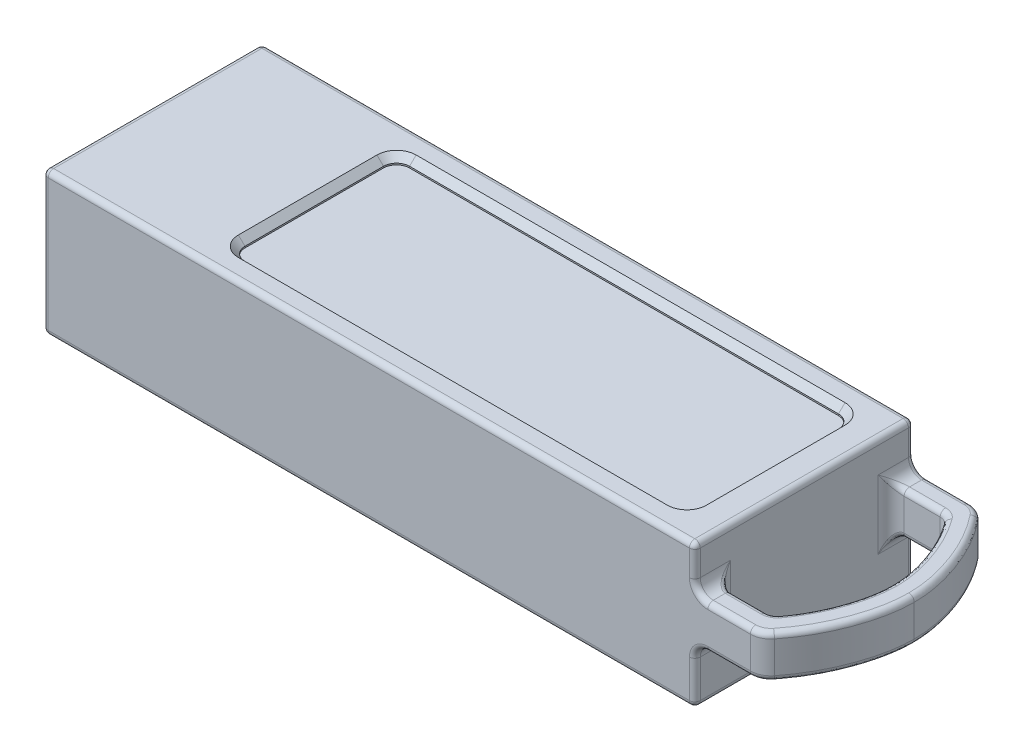
SolidWorks part; units mm, degrees
ref_plane "Front" through (0, 0, 0) normal (0, 0, 1) x (1, 0, 0)
ref_plane "Top" through (0, 0, 0) normal (0, 1, 0) x (1, 0, 0)
ref_plane "Right" through (0, 0, 0) normal (1, 0, 0) x (0, 0, -1)
sketch "Sketch1" plane through (0, 0, 0) normal (0, 1, 0) x (1, 0, 0)
  line L1 (-76.2, -25.6032) -> (76.2, -25.6032)
  line L2 (-76.2, -25.6032) -> (-76.2, 25.6032)
  line L3 (-76.2, 25.6032) -> (76.2, 25.6032)
  line L4 (76.2, -25.6032) -> (76.2, 25.6032)
  line L5 (-76.2, -25.6032) -> (76.2, 25.6032) construction
  line L6 (-76.2, 25.6032) -> (76.2, -25.6032) construction
  point P0 (0, 0)
  dimension "D1" = 51.2064
  dimension "D2" = 152.4
extrude "Boss-Extrude1" add sketch "Sketch1" along normal mid plane 33.401
sketch "Sketch3" plane through (0, 16.7005, 0) normal (0, 1, 0) x (1, 0, 0)
  line L0 (76.2, -25.6032) -> (76.2, 25.6032) construction
  line L1 (67.9831, 19.2405) -> (-38.3667, 19.2405)
  line L2 (67.9831, 19.2405) -> (67.9831, -19.2405)
  line L3 (67.9831, -19.2405) -> (-38.3667, -19.2405)
  line L4 (-38.3667, 19.2405) -> (-38.3667, -19.2405)
  point P6 (67.9831, 0)
  dimension "D1" = 8.2169
  dimension "D2" = 38.481
  dimension "D3" = 106.3498
extrude "Cut-Extrude1" cut sketch "Sketch3" against normal blind 1.8796
fillet "Fillet1" radius 3.048 4 edges at (67.9831, 15.7607, 19.2405) (67.9831, 15.7607, -19.2405) (-38.3667, 15.7607, 19.2405) (-38.3667, 15.7607, -19.2405)
chamfer "Chamfer2" distance 1.524 angle 45 8 edges at (67.9831, 16.7005, 0) (67.0904, 16.7005, -18.3478) (67.0904, 16.7005, 18.3478) (14.8082, 16.7005, -19.2405) (14.8082, 16.7005, 19.2405) (-37.474, 16.7005, -18.3478) (-37.474, 16.7005, 18.3478) (-38.3667, 16.7005, 0)
mirror "Mirror1" about plane through (0, 0, 0) normal (0, 1, 0) of "Cut-Extrude1", "Fillet1"
chamfer "Chamfer3" distance 1.524 angle 45 8 edges at (14.8082, -16.7005, -19.2405) (-37.474, -16.7005, -18.3478) (67.0904, -16.7005, -18.3478) (-38.3667, -16.7005, 0) (67.9831, -16.7005, 0) (-37.474, -16.7005, 18.3478) (67.0904, -16.7005, 18.3478) (14.8082, -16.7005, 19.2405)
sketch "Sketch4" plane through (-76.2, 0, 0) normal (-1, 0, 0) x (0, 0, 1)
  line L0 (-25.6032, -16.7005) -> (25.6032, -16.7005) construction
  line L1 (16.383, 4.1275) -> (-16.383, 4.1275)
  line L2 (19.685, 0.8255) -> (19.685, -8.3185)
  line L3 (16.383, -11.6205) -> (-16.383, -11.6205)
  line L4 (-19.685, 0.8255) -> (-19.685, -8.3185)
  arc A0 (19.685, -8.3185) -> (16.383, -11.6205) centre (16.383, -8.3185) cw
  arc A1 (-16.383, -11.6205) -> (-19.685, -8.3185) centre (-16.383, -8.3185) cw
  arc A2 (16.383, 4.1275) -> (19.685, 0.8255) centre (16.383, 0.8255) cw
  arc A3 (-16.383, 4.1275) -> (-19.685, 0.8255) centre (-16.383, 0.8255) ccw
  point P6 (0, 4.1275)
  point P10 (19.685, -11.6205)
  point P15 (19.685, 4.1275)
  point P18 (-19.685, 4.1275)
  point P19 (16.383, 4.1275)
  dimension "D4" = 3.302
  dimension "D1" = 15.748
  dimension "D2" = 5.08
  dimension "D3" = 39.37
split line "Split Line1"
sketch "Sketch5" plane through (-76.2, 0, 0) normal (-1, 0, 0) x (0, 0, 1)
  line L1 (-17.653, 1.4732) -> (0.3556, 1.4732)
  line L2 (-17.653, 1.4732) -> (-17.653, -8.9662)
  line L3 (-17.653, -8.9662) -> (0.3556, -8.9662)
  line L4 (0.3556, 1.4732) -> (0.3556, -8.9662)
  line L5 (-19.685, 0.8255) -> (-19.685, -8.3185) construction
  line L6 (19.685, -8.3185) -> (19.685, 0.8255) construction
  line L7 (3.429, 0.0635) -> (17.653, 0.0635)
  line L8 (3.429, 0.0635) -> (3.429, -7.5565)
  line L9 (3.429, -7.5565) -> (17.653, -7.5565)
  line L10 (17.653, 0.0635) -> (17.653, -7.5565)
  point P4 (-17.653, -3.7465)
  point P7 (-19.685, -3.7465)
  point P14 (3.429, -3.7465)
  point P15 (0.3556, -3.7465)
  dimension "D1" = 18.0086
  dimension "D2" = 10.4394
  dimension "D3" = 2.032
  dimension "D4" = 14.224
  dimension "D5" = 7.62
  dimension "D6" = 2.032
extrude "Cut-Extrude2" cut sketch "Sketch5" against normal blind 7.9375
fillet "Fillet3" radius 0.508 8 edges at (-72.2312, -7.5565, 17.653) (-72.2312, -7.5565, 3.429) (-72.2312, 0.0635, 17.653) (-72.2312, 0.0635, 3.429) (-72.2312, -8.9662, 0.3556) (-72.2312, -8.9662, -17.653) (-72.2312, 1.4732, 0.3556) (-72.2312, 1.4732, -17.653)
chamfer "Chamfer4" distance 0.762 angle 45 16 edges at (-76.2, -7.5565, 10.541) (-76.2, -7.4077, 17.5042) (-76.2, -7.4077, 3.5778) (-76.2, -3.7465, 17.653) (-76.2, -3.7465, 3.429) (-76.2, -0.0853, 17.5042) (-76.2, -0.0853, 3.5778) (-76.2, 0.0635, 10.541) (-76.2, -8.9662, -8.6487) (-76.2, -8.8174, 0.2068) (-76.2, -8.8174, -17.5042) (-76.2, -3.7465, 0.3556) (-76.2, -3.7465, -17.653) (-76.2, 1.3244, 0.2068) (-76.2, 1.3244, -17.5042) (-76.2, 1.4732, -8.6487)
sketch "Sketch6" plane through (-68.2625, 0, 0) normal (-1, 0, 0) x (0, 0, 1)
  line L0 (-17.653, 0.9652) -> (-17.653, -8.4582) construction
  line L1 (-16.383, -0.8128) -> (-12.9032, -0.8128)
  line L2 (-16.383, -0.8128) -> (-16.383, -6.6802)
  line L3 (-16.383, -6.6802) -> (-12.9032, -6.6802)
  line L4 (-17.653, 0.9652) -> (-17.653, -8.4582) construction
  arc A0 (-12.9032, -0.8128) -> (-12.9032, -6.6802) centre (-12.9032, -3.7465) cw
  circle A1 centre (-12.9032, -3.7465) radius 2.667
  circle A2 centre (-4.7498, -3.7465) radius 2.9464
  circle A3 centre (-4.7498, -3.7465) radius 2.667
  point P8 (-17.653, -3.7465)
  point P9 (-16.383, -3.7465)
  point P15 (-4.7498, -3.7465)
  point P16 (0, 0)
  dimension "D1" = 3.4798
  dimension "D4" = 5.334
  dimension "D5" = 2.2733
  dimension "D6" = 5.8928
  dimension "D7" = 5.334
  dimension "D2" = 5.8674
  dimension "D3" = 1.27
extrude "XT60 Connector Casing" add sketch "Sketch6" along normal offset from surface (7.4295 mm away) 0.508 contours A0 L1 L2 L3 A1 | A2 A3 region at (-68.2625, -0.8997, -14.6431) region at (-68.2625, -3.7465, -7.6129) up to face at (-76.2, 0, 0)
sketch "Sketch7" plane through (-68.2625, 0, 0) normal (-1, 0, 0) x (0, 0, 1)
  circle A24 centre (-12.9032, -3.7465) radius 2.413
  circle A25 centre (-12.9032, -3.7465) radius 2.413
  circle A26 centre (-12.9032, -3.7465) radius 2.159
  circle A27 centre (-4.7498, -3.7465) radius 2.413
  circle A28 centre (-4.7498, -3.7465) radius 2.413
  circle A29 centre (-4.7498, -3.7465) radius 2.159
  dimension "D1" = 0.254
  dimension "D2" = 0.254
  dimension "D3" = 0.254
  dimension "D4" = 0.254
extrude "XT60 Pins" add sketch "Sketch7" along normal offset from surface (6.9215 mm away) 0.508 up to face at (-75.692, -3.7465, -15.5702)
sketch "Sketch9" plane through (-68.2625, 0, 0) normal (-1, 0, 0) x (0, 0, 1)
  line L1 (6.9606, -0.9462) -> (7.547, -0.9462)
  line L2 (6.9606, -0.9462) -> (6.9606, -2.0955)
  line L3 (5.1308, -6.5469) -> (6.123, -6.5469)
  line L4 (7.547, -0.9462) -> (7.547, -2.0955)
  line L5 (13.535, -0.9462) -> (13.535, -2.0955)
  line L6 (8.6788, -2.8124) -> (9.6948, -2.8124)
  line L7 (5.1308, -2.0955) -> (15.9512, -2.0955)
  line L8 (5.1308, -2.0955) -> (5.1308, -5.3975)
  line L9 (5.1308, -5.3975) -> (15.9512, -5.3975)
  line L10 (15.9512, -2.0955) -> (15.9512, -5.3975)
  line L11 (6.123, -2.8124) -> (7.139, -2.8124)
  line L12 (6.123, -2.8124) -> (6.123, -3.8284)
  line L13 (6.123, -3.8284) -> (7.139, -3.8284)
  line L14 (7.139, -2.8124) -> (7.139, -3.8284)
  line L15 (8.6788, -2.8124) -> (8.6788, -3.8284)
  line L16 (8.6788, -3.8284) -> (9.6948, -3.8284)
  line L17 (9.6948, -2.8124) -> (9.6948, -3.8284)
  line L18 (11.2345, -2.8124) -> (12.2505, -2.8124)
  line L19 (11.2345, -2.8124) -> (11.2345, -3.8284)
  line L20 (11.2345, -3.8284) -> (12.2505, -3.8284)
  line L21 (12.2505, -2.8124) -> (12.2505, -3.8284)
  line L22 (13.7902, -2.8124) -> (14.8062, -2.8124)
  line L23 (13.7902, -2.8124) -> (13.7902, -3.8284)
  line L24 (13.7902, -3.8284) -> (14.8062, -3.8284)
  line L25 (14.8062, -2.8124) -> (14.8062, -3.8284)
  line L26 (14.1214, -0.9462) -> (14.1214, -2.0955)
  line L27 (5.1308, -6.5469) -> (5.1308, -5.3975)
  line L28 (6.123, -6.5469) -> (6.123, -5.3975)
  line L29 (7.139, -6.5469) -> (7.139, -5.3975)
  line L30 (8.6788, -6.5469) -> (8.6788, -5.3975)
  line L31 (9.6948, -6.5469) -> (9.6948, -5.3975)
  line L32 (11.2345, -6.5469) -> (11.2345, -5.3975)
  line L33 (12.2505, -6.5469) -> (12.2505, -5.3975)
  line L34 (13.7902, -6.5469) -> (13.7902, -5.3975)
  line L35 (14.8062, -6.5469) -> (14.8062, -5.3975)
  line L36 (10.541, -0.9462) -> (10.541, -6.5469) construction
  line L37 (15.9512, -6.5469) -> (15.9512, -5.3975)
  line L39 (13.535, -0.9462) -> (14.1214, -0.9462)
  line L40 (7.139, -6.5469) -> (8.6788, -6.5469)
  line L41 (9.6948, -6.5469) -> (11.2345, -6.5469)
  line L42 (12.2505, -6.5469) -> (13.7902, -6.5469)
  line L43 (14.8062, -6.5469) -> (15.9512, -6.5469)
  dimension "D3" = 3.302
  dimension "D4" = 1.016
  dimension "D5" = 1.016
  dimension "D6" = 4
extrude "Boss-Extrude4" add sketch "Sketch9" along normal offset from surface (6.4135 mm away) 1.524 contours L3 L28 L9 L27 | L36 L7 L8 L9 L11 L14 L13 L12 L6 L17 L16 L15 | L29 L40 L30 L9 | L9 L36 L41 L32 | L36 L9 L31 L41 | L7 L36 L9 L10 L22 L25 L24 L23 L18 L21 L20 L19 | L33 L42 L34 L9 | L35 L43 L37 L9 region at (-68.2625, -3.8022, 7.8264) region at (-68.2625, -3.8022, 13.2756) region at (-68.2625, -5.9722, 5.6269) region at (-68.2625, -5.9722, 10.1179) region at (-68.2625, -5.9722, 10.8877) region at (-68.2625, -5.9722, 7.9089) region at (-68.2625, -5.9722, 13.0203) region at (-68.2625, -5.9722, 15.3787) up to face at (-76.2, 0, 0)
extrude "Boss-Extrude6" add sketch "Sketch9<5>" along normal offset from surface (5.9055 mm away) 0.508 contours L2 L7 L4 L1 | L39 L5 L7 L26 region at (-68.2625, -1.5208, 7.2538) region at (-68.2625, -1.5208, 13.8282) up to face at (-74.676, -3.3204, 11.7425)
sketch "Sketch9<5>" plane through (-68.2625, 0, 0) normal (-1, 0, 0) x (0, 0, 1) same geometry as "Sketch9"
sketch "Sketch2" plane through (76.2, 0, 0) normal (1, 0, 0) x (0, 0, -1)
  line L0 (25.6032, 16.7005) -> (25.6032, -16.7005) construction
  line L1 (25.6032, 6.4008) -> (-25.6032, 6.4008)
  line L2 (25.6032, 6.4008) -> (25.6032, -3.5687)
  line L3 (25.6032, -3.5687) -> (-25.6032, -3.5687)
  line L4 (-25.6032, 6.4008) -> (-25.6032, -3.5687)
  line L5 (-25.6032, 16.7005) -> (25.6032, 16.7005) construction
  line L6 (-25.6032, 16.7005) -> (-25.6032, -16.7005) construction
  point P6 (19.4182, 25.0944)
  dimension "D1" = 9.9695
  dimension "D3" = 10.2997
extrude "Boss-Extrude7" add sketch "Sketch2" along normal blind 25.6794
sketch "Sketch10" plane through (0, 6.4008, 0) normal (0, 1, 0) x (1, 0, 0)
  line L0 (76.2, 0) -> (101.8794, 0) construction
  line L3 (76.2, 25.6032) -> (76.2, -25.6032) construction
  line L4 (101.8794, 25.6032) -> (101.8794, -25.6032) construction
  line L5 (76.2, 25.6032) -> (89.1783, 25.6032)
  line L7 (76.2, -25.6032) -> (89.1783, -25.6032)
  line L8 (76.2, 20.2692) -> (88.9311, 20.2692)
  line L9 (76.2, -20.2692) -> (88.9311, -20.2692)
  arc A0 (89.1783, 25.6032) -> (92.9662, 23.7676) centre (89.1783, 20.7772) cw
  arc A1 (89.1783, -25.6032) -> (92.9662, -23.7676) centre (89.1783, -20.7772) ccw
  arc A2 (88.9311, 20.2692) -> (88.9311, 20.2692) centre (88.9311, 20.2692) cw
  arc A3 (88.9311, -20.2692) -> (88.9311, -20.2692) centre (88.9311, -20.2692) ccw
  spline S0 degree 3 poles (92.9662, 23.7676) (96.1905, 19.6834) (100.1226, 12.1063) (101.8794, 3.6629) (101.8794, 0) knots 0.081239 0.081239 0.081239 0.081239 0.617185 1 1 1 1
  spline S1 degree 3 poles (92.9662, -23.7676) (96.1905, -19.6834) (100.1226, -12.1063) (101.8794, -3.6629) (101.8794, 0) knots 0.081239 0.081239 0.081239 0.081239 0.617185 1 1 1 1
  spline S2 degree 1 poles (88.9311, 20.2692) (96.5454, 0) knots 0 0 1 1 construction
  spline S3 degree 3 poles (88.9311, 20.2692) (89.5161, 19.5183) (90.6376, 17.9584) (92.57, 14.7795) (94.4989, 10.5947) (96.1315, 5.2293) (96.5454, 1.7631) (96.5454, 0) knots 0.090867 0.090867 0.090867 0.090867 0.204508 0.31815 0.545433 0.772717 1 1 1 1
  spline S4 degree 1 poles (88.9311, -20.2692) (96.5454, 0) knots 0 0 1 1 construction
  spline S5 degree 3 poles (88.9311, -20.2692) (89.5161, -19.5183) (90.6376, -17.9584) (92.57, -14.7795) (94.4989, -10.5947) (96.1315, -5.2293) (96.5454, -1.7631) (96.5454, 0) knots 0.090867 0.090867 0.090867 0.090867 0.204508 0.31815 0.545433 0.772717 1 1 1 1
  line M3 (76.2, 25.6032) -> (76.2, -25.6032)
  line M4 (76.2, -25.6032) -> (101.8794, -25.6032)
  line M5 (101.8794, -25.6032) -> (101.8794, 25.6032)
  line M6 (101.8794, 25.6032) -> (76.2, 25.6032)
  dimension "D1" = 4.826
  dimension "D2" = 5.334
  dimension "D3" = 5.334
extrude "Cut-Extrude3" cut sketch "Sketch10" against normal up to next contours L9 S5 S3 L8 M3 | S1 A1 M4 M5 | A0 S0 M5 M6
fillet "Fillet4" radius 2.54 2 edges at (88.9311, 1.416, 20.2692) (88.9311, 1.416, -20.2692)
fillet "Fillet5" radius 3.048 6 edges at (76.2, 6.4008, -22.9362) (76.2, -3.5687, -22.9362) (76.2, -3.5687, 22.9362) (76.2, 6.4008, 22.9362) (76.2, 1.416, -20.2692) (76.2, 1.416, 20.2692)
fillet "Fillet6" radius 1.27 36 edges at (77.0927, -4.4614, 19.3765) (83.4553, -3.5687, 20.2692) (88.8177, -3.5687, 19.9914) (77.0927, -4.4614, -19.3765) (83.4553, -3.5687, -20.2692) (88.8177, -3.5687, -19.9914) (77.0927, 7.2935, -19.3765) (83.4553, 6.4008, -20.2692) (88.8177, 6.4008, -19.9914) (77.0927, 7.2935, 19.3765) (83.4553, 6.4008, 20.2692) (88.8177, 6.4008, 19.9914) (76.2, 13.0746, 25.6032) (77.0927, 7.2935, 25.6032) (84.2132, 6.4008, 25.6032) (91.2829, 6.4008, 25.1201) (91.2829, 6.4008, -25.1201) (84.2132, 6.4008, -25.6032) (77.0927, 7.2935, -25.6032) (76.2, -11.6586, 25.6032) (77.0927, -4.4614, 25.6032) (84.2132, -3.5687, 25.6032) (91.2829, -3.5687, 25.1201) (91.2829, -3.5687, -25.1201) (84.2132, -3.5687, -25.6032) (77.0927, -4.4614, -25.6032) (76.2, 13.0747, -25.6032) (76.2, -11.6586, -25.6032)
fillet "Outer Fillet" radius 1.27 14 edges at (-0.635, 16.7005, 25.6032) (-76.2, 16.7005, 0) (-0.635, 16.7005, -25.6032) (76.2, 16.7005, 0) (76.2, -16.7005, 0) (-0.635, -16.7005, 25.6032) (-76.2, -16.7005, 0) (-0.635, -16.7005, -25.6032) (-76.2, 0, -25.6032) (-76.2, 0, 25.6032) (75.828, -16.7005, 25.2312) (75.828, -16.7005, -25.2312) (75.828, 16.7005, -25.2312) (75.828, 16.7005, 25.2312)
